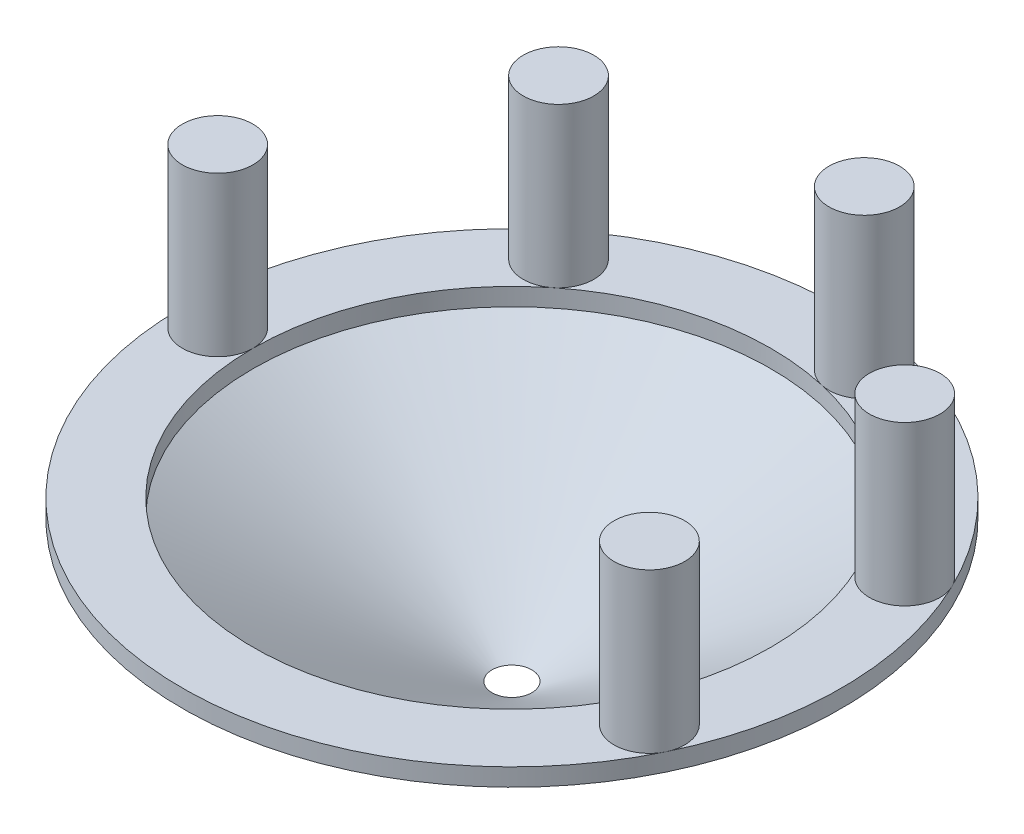
SolidWorks part; units mm, degrees
ref_plane "Front Plane" through (0, 0, 0) normal (0, 0, 1) x (1, 0, 0)
ref_plane "Top Plane" through (0, 0, 0) normal (0, 1, 0) x (1, 0, 0)
ref_plane "Right Plane" through (0, 0, 0) normal (1, 0, 0) x (0, 0, -1)
sketch "Sketch1" plane through (0, 0, 0) normal (0, 0, 1) x (1, 0, 0)
  line L0 (0, -582.4468) -> (0, 28539.8911) construction
  line L2 (28, 0) -> (3.175, -12)
  line L3 (3.175, -12) -> (1.686, -12)
  line L4 (1.686, -12) -> (22, 0)
  line L5 (1.686, -12) -> (0, -12) construction
  line L6 (22, 0) -> (0, 0) construction
  line L7 (22, 0) -> (22, 1.5)
  line L8 (22, 1.5) -> (28, 1.5)
  line L9 (28, 1.5) -> (28, 0)
  dimension "D1" = 1.489
  dimension "D2" = 1.686
  dimension "D3" = 22
  dimension "D4" = 6
  dimension "D5" = 12
  dimension "D6" = 1.5
revolve "Revolve1" add sketch "Sketch1" angle 360 about L0
sketch "Sketch3" plane through (0, 0, 0) normal (0, 1, 0) x (1, 0, 0)
  line L0 (-22, 0) -> (-28, 0) construction
  circle A1 centre (0, 0) radius 22 construction
  circle A2 centre (0, 0) radius 22 construction
  circle A3 centre (0, 0) radius 28 construction
  circle A4 centre (-25, 0) radius 3
extrude "Boss-Extrude1" add sketch "Sketch3" along normal blind 15
pattern_circular "CirPattern1" count 5 every 51.429 about axis through (0, 0, 0) along (0, -1, 0) of "Boss-Extrude1"
